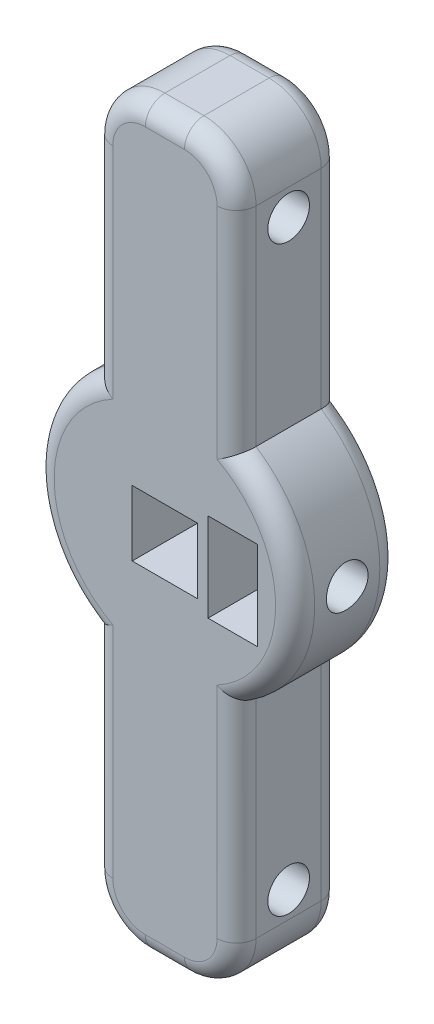
SolidWorks part; units mm, degrees
ref_plane "Front Plane" through (0, 0, 0) normal (0, 0, 1) x (1, 0, 0)
ref_plane "Top Plane" through (0, 0, 0) normal (0, 1, 0) x (1, 0, 0)
ref_plane "Right Plane" through (0, 0, 0) normal (1, 0, 0) x (0, 0, -1)
sketch "Sketch2" plane through (0, 0, 0) normal (0, 0, 1) x (1, 0, 0)
  line L0 (0, -167.7125) -> (0, 36.0066) construction
  line L5 (-6.985, 10.6066) -> (-6.985, 36.0066)
  line L6 (-6.985, 36.0066) -> (6.985, 36.0066)
  line L7 (6.985, 36.0066) -> (6.985, 10.6066)
  line L8 (-74.2931, 0) -> (71.2723, 0) construction
  line L9 (6.985, -36.0066) -> (6.985, -10.6066)
  line L15 (-6.985, -36.0066) -> (6.985, -36.0066)
  line L16 (-6.985, -10.6066) -> (-6.985, -36.0066)
  circle A1 centre (0, 0) radius 2.032
  circle A4 centre (0, 0) radius 12.7 construction
  arc A5 (-6.985, 10.6066) -> (-6.985, -10.6066) centre (0, 0) ccw
  arc A9 (6.985, -10.6066) -> (6.985, 10.6066) centre (0, 0) ccw
  dimension "D4" = 4.064
  dimension "D1" = 25.4
  dimension "D5" = 25.4
  dimension "D6" = 13.97
extrude "Boss-Extrude1" add sketch "Sketch2" along normal blind 10.16
sketch "Sketch3" plane through (0, 0, 0) normal (0, 0, -1) x (-1, 0, 0)
  line L1 (-3.19, 3.19) -> (3.19, 3.19)
  line L2 (-3.19, 3.19) -> (-3.19, -3.19)
  line L3 (-3.19, -3.19) -> (3.19, -3.19)
  line L4 (3.19, 3.19) -> (3.19, -3.19)
  line L5 (-3.19, 3.19) -> (3.19, -3.19) construction
  line L6 (-3.19, -3.19) -> (3.19, 3.19) construction
  point P0 (0, 0)
  dimension "D1" = 6.38
  dimension "D2" = 6.38
extrude "Cut-Extrude1" cut sketch "Sketch3" against normal through all
sketch "Sketch4" plane through (6.985, 0, 3.175) normal (-1, 0, 0) x (0, 0, 1)
  line L2 (6.985, 36.0066) -> (-3.175, 36.0066) construction
  line L3 (6.985, -36.0066) -> (-3.175, -36.0066) construction
  circle A0 centre (1.905, 28.3866) radius 2.032
  circle A1 centre (1.905, -28.3866) radius 2.032
  point P12 (1.905, 36.0066)
  dimension "D2" = 4.064
  dimension "D1" = 7.62
  dimension "D3" = 7.62
extrude "Cut-Extrude2" cut sketch "Sketch4" along normal blind 24.13
fillet "Fillet3" radius 1.905 16 edges at (6.985, -23.3066, 0) (12.7, 0, 0) (6.985, 23.3066, 0) (0, 36.0066, 0) (-6.985, 23.3066, 0) (-12.7, 0, 0) (-6.985, -23.3066, 0) (0, -36.0066, 0) (0, -36.0066, 10.16) (0, 36.0066, 10.16) (-6.985, 23.3066, 10.16) (-6.985, -23.3066, 10.16) (-12.7, 0, 10.16) (6.985, -23.3066, 10.16) (12.7, 0, 10.16) (6.985, 23.3066, 10.16)
fillet "Fillet1" radius 5.08 12 edges at (-6.985, -36.0066, 5.08) (-6.985, 36.0066, 5.08) (6.985, 36.0066, 5.08) (6.985, -36.0066, 5.08) (6.427, -35.4486, 0.558) (6.427, -35.4486, 9.602) (6.427, 35.4486, 0.558) (6.427, 35.4486, 9.602) (-6.427, 35.4486, 0.558) (-6.427, 35.4486, 9.602) (-6.427, -35.4486, 0.558) (-6.427, -35.4486, 9.602)
sketch "Sketch5" plane through (3.19, 0, 0) normal (-1, 0, 0) x (0, 0, 1)
  line L0 (8.255, -10.6066) -> (8.255, 10.6066) construction
  line L1 (8.255, -10.6066) -> (1.905, -10.6066) construction
  circle A0 centre (5.08, 0) radius 2.032
  point P5 (8.255, 0)
  point P8 (5.08, -10.6066)
  dimension "D1" = 4.064
extrude "Cut-Extrude3" cut sketch "Sketch5" against normal through all
sketch "Sketch7" plane through (3.19, 0, 0) normal (-1, 0, 0) x (0, 0, 1)
  line L1 (0, 4.318) -> (10.16, 4.318)
  line L2 (0, 4.318) -> (0, -4.318)
  line L3 (0, -4.318) -> (10.16, -4.318)
  line L4 (10.16, 4.318) -> (10.16, -4.318)
  line L5 (10.16, 3.19) -> (10.16, -3.19) construction
  line L10 (0, 3.19) -> (0, -3.19) construction
  point P4 (0, -7.9487)
  point P5 (1.0706, 3.1786)
  point P7 (0, 0)
  point P9 (0, 0)
  point P10 (0, 0)
  point P11 (0, 0)
  point P12 (0, 0)
  point P13 (8.0055, 3.8742)
  point P15 (0, -3.19)
  point P17 (10.16, 0)
  dimension "D1" = 8.636
extrude "Cut-Extrude4" cut sketch "Sketch7" against normal blind 5.842
sketch "Sketch8" plane through (3.19, 0, 0) normal (1, 0, 0) x (0, 0, -1)
  line L1 (0, 4.318) -> (-10.16, 4.318)
  line L2 (0, 4.318) -> (0, -4.318)
  line L3 (0, -4.318) -> (-10.16, -4.318)
  line L4 (-10.16, 4.318) -> (-10.16, -4.318)
extrude "Boss-Extrude2" add sketch "Sketch8" along normal blind 1.016
